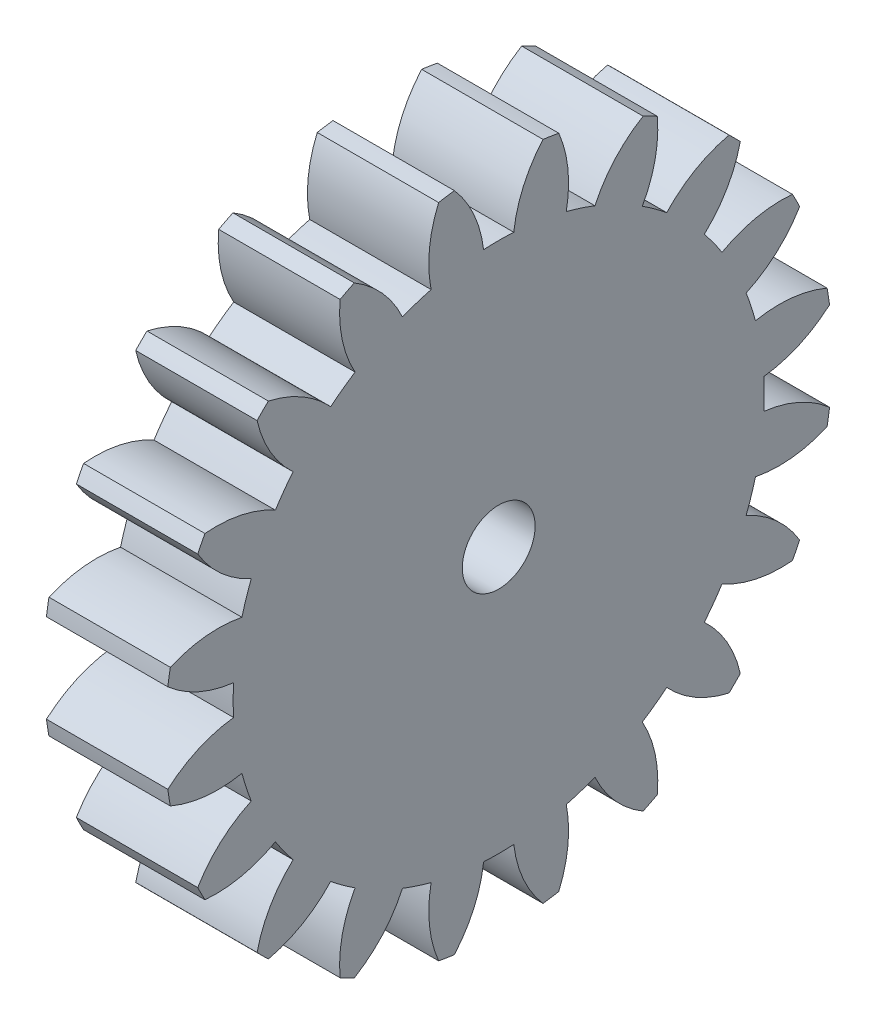
SolidWorks part; units mm, degrees
ref_plane "Plane1" through (0, 0, 0) normal (0, 0, 1) x (1, 0, 0)
ref_plane "Plane2" through (0, 0, 0) normal (0, 1, 0) x (1, 0, 0)
ref_plane "Plane3" through (0, 0, 0) normal (1, 0, 0) x (0, 0, -1)
sketch "HoldingSke" plane through (0, 0, 0) normal (0, 1, 0) x (1, 0, 0)
  line L0 (0, 0) -> (0.7518, -0.2736)
  line L1 (-15, 0) -> (100, 0) construction
  line L2 (0, 0) -> (-2.1039, 2.3779)
  line L3 (0, 0) -> (-11.863, 4.5341)
  line L4 (0, 0) -> (8.1152, 2.9537)
  line L5 (0, 0) -> (-46.8476, -17.4728)
  line L6 (0, 0) -> (-9.9476, -6.7116)
  line L7 (-2.1039, 2.3779) -> (8.6586, 51.2059)
  line L8 (-76.2, 54.61) -> (-75.7, 54.61)
  line L9 (-71.009, 38.7566) -> (-53.1078, 45.2721)
  line L10 (-76.2, 71.12) -> (104.1128, 71.12)
  line L11 (0, 0) -> (-12, 0)
  line L12 (-76.2, 101.6) -> (-76.155, 101.6)
  line L13 (24.9733, 27.94) -> (52.9518, 28.4284)
  line L14 (24.9733, 27.94) -> (24.9743, 27.94)
  line L15 (24.9733, 27.94) -> (100.4006, 29.5858)
  line L16 (-63.627, -1.25) -> (-12.827, -1.25)
  circle A0 centre (0, 0) radius 1.5
  circle A1 centre (0, 0) radius 10.9365
  circle A2 centre (0, 0) radius 37.5
  circle A3 centre (0, 0) radius 1.5
  dimension "Num_teeth" = 20
  dimension "Pitch_radius" = 180.3128
  dimension "Width" = 12
  dimension "Thickness" = 12
sketch "BasProSke" plane through (0, 0, 0) normal (0, 1, 0) x (1, 0, 0)
  line L0 (-10, 0) -> (60, 0) construction
  line L1 (0, 0) -> (0, 13.75)
  line L2 (0, 0) -> (12, 0)
  line L3 (12, 0) -> (12, 13.75)
  line L4 (12, 13.75) -> (0, 13.75)
  dimension "Thickness" = 12
  dimension "Diameter" = 27.5
revolve "Base-Revolve" add sketch "BasProSke" angle 360 about L0
sketch "TooCutSke" plane through (0, 0, 0) normal (1, 0, 0) x (0, 0, -1)
  line L1 (0, 0) -> (0, 107) construction
  line L2 (0, 0) -> (-1.0594, 12.455) construction
  line L3 (0, 0) -> (-3.9007, 24.6278) construction
  line L4 (-1.0594, 12.455) -> (-1.9503, 12.3139) construction
  arc A0 (0.6211, 10.9188) -> (-0.6211, 10.9188) centre (0, 0) ccw
  arc A1 (1.8466, 13.6511) -> (-1.8466, 13.6511) centre (0, 0) ccw
  circle A2 centre (0, 0) radius 12.5 construction
  circle A3 centre (0, 0) radius 11.7462 construction
  arc A4 (-0.6211, 10.9188) -> (-1.8466, 13.6511) centre (-5.5866, 10.3326) ccw
  arc A5 (1.8466, 13.6511) -> (0.6211, 10.9188) centre (5.5866, 10.3326) ccw
extrude "ToothCut" cut sketch "TooCutSke" along normal through all
fillet "Breaks" [suppressed] radius 0.025 tangent propagation no
fillet "RootFillets" [suppressed] radius 0.3135
pattern_circular "TeethCuts" count 20 every 18 about axis through (-10, 0, 0) along (1, 0, 0) of "ToothCut", "RootFillets", "Breaks"
sketch "HubNeaOneSke" plane through (0, 0, 0) normal (-1, 0, 0) x (0, 0, 1)
  circle A0 centre (0, 0) radius 10.9365
  dimension "Diameter" = 21.873
extrude "HubNearOne" [suppressed] add sketch "HubNeaOneSke" along normal blind 38.0001
sketch "HubNeaBotSke" plane through (0, 0, 0) normal (-1, 0, 0) x (0, 0, 1)
  circle A0 centre (0, 0) radius 10.9365
  dimension "Diameter" = 21.873
extrude "HubNearBoth" [suppressed] add sketch "HubNeaBotSke" along normal blind 19
ref_plane "FarPln" through (12, 0, 0) normal (1, 0, 0) x (0, 0, -1)
sketch "HubFarSke" plane through (12, 0, 0) normal (1, 0, 0) x (0, 0, -1)
  circle A0 centre (0, 0) radius 10.9365
  dimension "Diameter" = 21.873
extrude "HubFar" [suppressed] add sketch "HubFarSke" along normal blind 19
sketch "BorSke" plane through (0, 0, 0) normal (1, 0, 0) x (0, 0, -1)
  circle A0 centre (0, 0) radius 1.5
  dimension "Diameter" = 3
extrude "Bore" cut sketch "BorSke" along normal mid plane 100.0001
sketch "KeySke" plane through (0, 0, 0) normal (1, 0, 0) x (0, 0, -1)
  line L0 (-0.6, 0) -> (-0.6, 2)
  line L1 (-0.6, 2) -> (0.6, 2)
  line L2 (0.6, 2) -> (0.6, 0)
  line L3 (0, 0) -> (0, 34) construction
  line L4 (-0.6, 0) -> (0.6, 0)
extrude "Keyway" [suppressed] cut sketch "KeySke" along normal mid plane 100.0001
pattern_circular "Keyway2" [suppressed] count 2 every 90 about axis through (-10, 0, 0) along (1, 0, 0) reverse direction yes
sketch "草圖1" plane through (12, 0, 0) normal (1, 0, 0) x (0, 0, -1)
  circle A0 centre (0, 0) radius 18
  dimension "D1" = 36
extrude "除料-伸長1" cut sketch "草圖1" against normal blind 7
equation "' \"Module@HoldingSke\" = 6.35"
equation "' \"Num_teeth@HoldingSke\" = 12"
equation "' \"Ap@HoldingSke\" =  20"
equation "' \"Ap@HoldingSke\" = 20"
equation "' \"Width@HoldingSke\" = 0.5 * 25.4"
equation "' \"Hub_dia@HoldingSke\"= 1 * 25.4"
equation "' \"Hub_dia@HoldingSke\" = 1 * 25.4"
equation "' \"Overall_len@HoldingSke\" = 1.0 * 25.4"
equation "' \"Bore@HoldingSke\" = 0.75 * 25.4"
equation "' \"T_dim@HoldingSke\" = 0.1 * 25.4"
equation "' \"Width@KeySke\" = 0.25 * 25.4"
equation "' \"Show_teeth@HoldingSke\" = 13"
equation "' \"Backlash@HoldingSke\" = 0.009 * 25.4"
equation "' \"Addendum_fac@HoldingSke\" = 1.0"
equation "' \"Dedendum_fac@HoldingSke\" = 1.25"
equation "' \"Dedendum_add@HoldingSke\" = 0.00005 * 25.4"
equation "' \"Clearance_fac@HoldingSke\" = 0.25"
equation "\"Pitch@HoldingSke\" = 1 / \"Module@HoldingSke\""
equation "\"Overcut_dia@TooCutSke\" = (\"Num_teeth@HoldingSke\" + 2 * \"Addendum_fac@HoldingSke\") / \"Pitch@HoldingSke\" + 0.002 * 25.4"
equation "\"Pitch_dia@TooCutSke\" = \"Num_teeth@HoldingSke\" / \"Pitch@HoldingSke\""
equation "\"Base_dia@TooCutSke\" = \"Num_teeth@HoldingSke\" / \"Pitch@HoldingSke\" * cos((\"Ap@HoldingSke\"  * 3.14159265 / 180))"
equation "\"Root_dia@TooCutSke\" = (\"Num_teeth@HoldingSke\" + 2) / \"Pitch@HoldingSke\" - 2 * (\"Addendum_fac@HoldingSke\" + \"Dedendum_fac@HoldingSke\") / \"Pitch@HoldingSke\" - \"Dedendum_add@HoldingSke\" * 2"
equation "\"Half_ang@TooCutSke\" = 180 / \"Num_teeth@HoldingSke\""
equation "\"Half_CT@TooCutSke\" = \"Num_teeth@HoldingSke\" / \"Pitch@HoldingSke\" * sin((3.14159265 / 2 / \"Num_teeth@HoldingSke\")) / 2 - 7 * \"Backlash@HoldingSke\" / 4"
equation "\"Flank_rad@TooCutSke\" = \"Num_teeth@HoldingSke\" / \"Pitch@HoldingSke\" / 5"
equation "\"Radius@RootFillets\" = \"Clearance_fac@HoldingSke\" / \"Pitch@HoldingSke\" + \"Dedendum_add@HoldingSke\""
equation "\"Break_rad@Breaks\" = 0.02 / \"Pitch@HoldingSke\""
equation "\"Thickness@HoldingSke\" = \"Width@HoldingSke\""
equation "\"OAL@HoldingSke\" = \"Thickness@HoldingSke\""
equation "\"MHD@HoldingSke\" = (\"Num_teeth@HoldingSke\" + 2) / \"Pitch@HoldingSke\" - 2 * (\"Addendum_fac@HoldingSke\" + \"Dedendum_fac@HoldingSke\")  / \"Pitch@HoldingSke\" - \"Dedendum_add@HoldingSke\" * 2"
equation "\"MBD@HoldingSke\" = (\"Num_teeth@HoldingSke\" + 2) / \"Pitch@HoldingSke\" - 2 * (\"Addendum_fac@HoldingSke\" + \"Dedendum_fac@HoldingSke\")  / \"Pitch@HoldingSke\" - \"Dedendum_add@HoldingSke\" * 2 - 0.002 * 25.4"
equation "\"MHD@HoldingSke\" = ((sgn( \"MHD@HoldingSke\" - \"Hub_dia@HoldingSke\" )-1)*( \"MHD@HoldingSke\" - \"Hub_dia@HoldingSke\" ))/-2+ \"Hub_dia@HoldingSke\""
equation "\"MBD@HoldingSke\" = ((sgn( \"MBD@HoldingSke\" - \"Bore@HoldingSke\" )-1)*( \"MBD@HoldingSke\" - \"Bore@HoldingSke\" ))/-2+ \"Bore@HoldingSke\""
equation "\"OAL@HoldingSke\" = ((sgn( \"OAL@HoldingSke\" - \"Overall_len@HoldingSke\" )+1)*( \"OAL@HoldingSke\" - \"Overall_len@HoldingSke\" ))/2 + \"Overall_len@HoldingSke\" + 0.000002 * 25.4"
equation "\"Num_teeth@TeethCuts\" = int( \"Show_teeth@HoldingSke\" ) + 1"
equation "\"Num_teeth@TeethCuts\" = ((sgn( \"Num_teeth@TeethCuts\" - \"Num_teeth@HoldingSke\" )-1)*( \"Num_teeth@TeethCuts\" - \"Num_teeth@HoldingSke\" ))/-2+ \"Num_teeth@HoldingSke\""
equation "\"Num_teeth@TeethCuts\" = ((sgn( \"Num_teeth@TeethCuts\" - 2.0)+1)*( \"Num_teeth@TeethCuts\" - 2.0))/2 +2.0"
equation "\"Angle@TeethCuts\" = 360.0 / \"Num_teeth@HoldingSke\""
equation "\"Diameter@BasProSke\" = (\"Num_teeth@HoldingSke\" + 2 * \"Addendum_fac@HoldingSke\") / \"Pitch@HoldingSke\""
equation "\"Thickness@BasProSke\"  = \"Thickness@HoldingSke\""
equation "' \"Fillet_rad@BasProSke\" =  \"Thickness@HoldingSke\" * 0.05"
equation "' \"Fillet_rad@BasProSke\" = \"Thickness@HoldingSke\" * 0.05"
equation "\"MHD@HoldingSke\" = ((sgn( \"MHD@HoldingSke\" - \"Root_dia@TooCutSke\" )-1)*( \"MHD@HoldingSke\" - \"Root_dia@TooCutSke\" ))/-2+ \"Root_dia@TooCutSke\""
equation "\"Diameter@HubNeaOneSke\" = \"MHD@HoldingSke\""
equation "\"Length@HubNearOne\" = \"OAL@HoldingSke\" - \"Thickness@BasProSke\""
equation "\"Diameter@HubNeaBotSke\" = \"MHD@HoldingSke\""
equation "\"Length@HubNearBoth\" = ( \"OAL@HoldingSke\" - \"Thickness@BasProSke\" ) / 2.0"
equation "\"Thickness@FarPln\" = \"Thickness@BasProSke\""
equation "\"Diameter@HubFarSke\" = \"MHD@HoldingSke\""
equation "\"Length@HubFar\" = ( \"OAL@HoldingSke\" - \"Thickness@BasProSke\" ) / 2.0"
equation "\"Diameter@BorSke\" = \"MBD@HoldingSke\""
equation "\"D1@Bore\" = \"OAL@HoldingSke\" * 2.0"
equation "\"D1@Keyway\" = \"OAL@HoldingSke\" * 2.0"
equation "\"Offset@KeySke\" = \"T_dim@HoldingSke\" + \"MBD@HoldingSke\" / 2.0"
